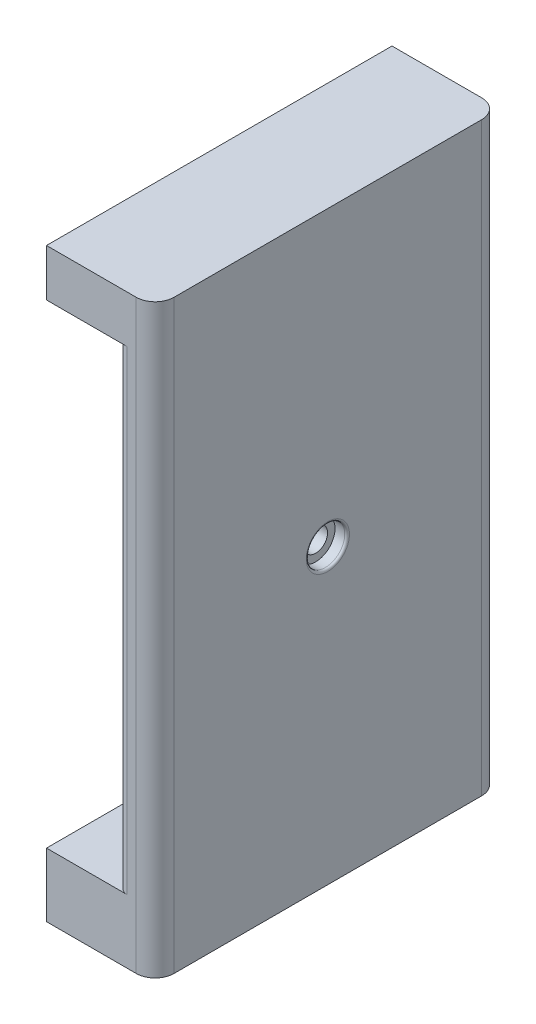
SolidWorks part; units mm, degrees
note: The reader was unsure of these and kept them because the rebuilt part matched: shared geometry of "Sketch12<6>".
other "Markup1"
sketch "Sketch9" plane through (-25.745, 62.7203, -36.576) normal (-0.5706, 0.1284, -0.8112) x (-0.8147, 0.0363, 0.5788)
ref_plane "Front Plane" through (0, 0, 0) normal (0, 0, 1) x (1, 0, 0)
ref_plane "Top Plane" through (0, 0, 0) normal (0, 1, 0) x (1, 0, 0)
ref_plane "Right Plane" through (0, 0, 0) normal (1, 0, 0) x (0, 0, -1)
sketch "Sketch1" plane through (0, 0, 0) normal (0, 0, 1) x (1, 0, 0)
  line L0 (8.255, 0) -> (-8.255, 0) construction
  line L1 (20.255, 0) -> (-20.255, 0) construction
  line L2 (8.255, 0) -> (8.255, 18.25)
  line L3 (8.255, 18.25) -> (20.255, 18.25)
  line L4 (20.255, 18.25) -> (20.255, 0)
  line L5 (8.255, 0) -> (20.255, 0)
  point P4 (0, 0)
  point P8 (0, 0)
  dimension "D1" = 16.51
  dimension "D2" = 12
  dimension "D3" = 18.25
revolve "Revolve1" add sketch "Sketch1" angle 360 about L5
sketch "Sketch2" plane through (8.255, 0, 0) normal (-1, 0, 0) x (0, 0, 1)
  circle A0 centre (0, 0) radius 3.7145
  dimension "D1" = 7.429
extrude "Cut-Extrude1" cut sketch "Sketch2" against normal blind 8.5725
sketch "Sketch3" plane through (20.255, 0, 0) normal (1, 0, 0) x (0, 0, -1)
  line L1 (13.175, -55) -> (-13.175, -55) construction
  line L2 (13.175, -55) -> (13.175, 55) construction
  line L3 (13.175, 55) -> (-13.175, 55) construction
  line L4 (-13.175, -55) -> (-13.175, 55) construction
  line L5 (13.175, -55) -> (-13.175, 55) construction
  line L6 (13.175, 55) -> (-13.175, -55) construction
  line L14 (6.6, 0) -> (-6.6, 0) construction
  line L15 (13.175, -55) -> (-13.175, 55) construction
  line L16 (13.175, 55) -> (-13.175, -55) construction
  line L17 (13.175, 55) -> (-13.175, 55) construction
  line L28 (-36.576, 0) -> (36.576, 0) construction
  line L33 (36.576, -62) -> (-36.576, -62)
  line L34 (36.576, -62) -> (36.576, 62)
  line L35 (36.576, 62) -> (-36.576, 62)
  line L36 (-36.576, -62) -> (-36.576, 62)
  line L37 (36.576, -62) -> (-36.576, 62) construction
  line L38 (36.576, 62) -> (-36.576, -62) construction
  point P0 (0, 0)
  point P11 (0, 0)
  point P12 (0, 0)
  dimension "D3" = 124
  dimension "D4" = 73.152
  dimension "D9" = 110
  dimension "D1" = 73.152
  dimension "D2" = 26.35
extrude "Boss-Extrude1" add sketch "Sketch3" along normal blind 8 separate body
sketch "Sketch4" plane through (20.255, 0, 0) normal (-1, 0, 0) x (0, 0, 1)
  line L0 (-19.575, 55) -> (-6.775, 55) construction
  line L1 (13.175, -55) -> (-13.175, -55) construction
  line L2 (13.175, -55) -> (13.175, 55) construction
  line L3 (13.175, 55) -> (-13.175, 55) construction
  line L4 (-13.175, -55) -> (-13.175, 55) construction
  line L5 (13.175, -55) -> (-13.175, 55) construction
  line L6 (13.175, 55) -> (-13.175, -55) construction
  circle A0 centre (-13.175, 55) radius 4.75
  circle A1 centre (13.175, -55) radius 4.75
  circle A2 centre (13.175, 55) radius 4.75
  circle A3 centre (-13.175, -55) radius 4.75
  circle A5 centre (-13.175, 55) radius 6.4
  circle A6 centre (13.175, 55) radius 6.4
  circle A7 centre (13.175, -55) radius 6.4
  circle A8 centre (-13.175, -55) radius 6.4
  point P6 (0, 0)
  dimension "D1" = 9.5
  dimension "D2" = 12.8
  dimension "D3" = 26.35
  dimension "D4" = 110
sketch "Sketch5" plane through (8.255, 0, 0) normal (-1, 0, 0) x (0, 0, 1)
  circle A0 centre (0, 0) radius 18.25
  dimension "D1" = 36.5
fillet "Fillet1" radius 4 2 edges at (28.255, 0, -36.576) (28.255, 0, 36.576)
sketch "Sketch6" plane through (8.255, 0, 0) normal (-1, 0, 0) x (0, 0, 1)
  circle A2 centre (0, 0) radius 13.15
  dimension "D1" = 26.3
extrude "Cut-Extrude2" cut sketch "Sketch6" against normal blind 12
ref_plane "Plane1" through (0, 0, 38) normal (0, 0, 1) x (1, 0, 0)
ref_plane "Plane2" through (19.255, 0, 0) normal (-1, 0, 0) x (0, 0, 1)
sketch "Sketch12" plane through (28.255, 0, 0) normal (1, 0, 0) x (0, 0, -1)
  circle A0 centre (0, 0) radius 4.075
  circle A1 centre (0, 0) radius 2.5
  dimension "D1" = 8.15
  dimension "D2" = 5
extrude "Cut-Extrude6" cut sketch "Sketch12" against normal blind 2.56 contours A0
extrude "Cut-Extrude7" cut sketch "Sketch12<6>" against normal up to surface (8 mm away) contours A1 up to face at (20.255, 0, 0)
sketch "Sketch12<6>" plane through (28.255, 0, 0) normal (1, 0, 0) x (0, 0, -1) same geometry as "Sketch12"
fillet "Fillet2" radius 0.5 1 edges at (28.255, 4.075, 0)
combine bodies "Combine1" operation type add bodies to combine 124 127
sketch "Sketch13" plane through (20.255, 0, 0) normal (-1, 0, 0) x (0, 0, 1)
  line L0 (-36.576, -62) -> (-36.576, 62) construction
  line L6 (-36.576, -48.5) -> (36.576, -48.5)
  line L7 (-36.576, -48.5) -> (-36.576, -62)
  line L8 (-36.576, -62) -> (36.576, -62)
  line L9 (36.576, -48.5) -> (36.576, -62)
  line L10 (36.576, -62) -> (36.576, 62) construction
  line L11 (-36.576, -62) -> (36.576, -62) construction
  line L13 (-36.576, 62) -> (36.576, 62)
  line L14 (-36.576, 62) -> (-36.576, 52)
  line L15 (-36.576, 52) -> (36.576, 52)
  line L16 (36.576, 62) -> (36.576, 52)
  dimension "D1" = 13.5
  dimension "D2" = 10
extrude "Boss-Extrude3" add sketch "Sketch13" along normal blind 15
fillet "Fillet3" radius 2 3 edges at (20.255, 1.75, -36.576) (20.255, -18.25, 0) (20.255, 1.75, 36.576)
sketch "Sketch14" plane through (0, -62, 0) normal (0, -1, 0) x (1, 0, 0)
  line L0 (28.255, 0) -> (-41.715, 0) construction
  line L1 (28.255, -32.576) -> (28.255, 32.576) construction
  line L3 (18.52, -12.75) -> (-31.98, -12.75) construction
  line L4 (18.52, -12.75) -> (18.52, 12.75) construction
  line L5 (18.52, 12.75) -> (-31.98, 12.75) construction
  line L6 (-31.98, -12.75) -> (-31.98, 12.75) construction
  line L7 (18.52, -12.75) -> (-31.98, 12.75) construction
  line L8 (18.52, 12.75) -> (-31.98, -12.75) construction
  circle A0 centre (18.52, 12.75) radius 3.7138
  circle A1 centre (18.52, -12.75) radius 3.7138
  point P6 (-6.73, 0)
  dimension "D4" = 7.4275
  dimension "D1" = 69.97
  dimension "D2" = 50.5
  dimension "D3" = 25.5
extrude "Cut-Extrude8" cut sketch "Sketch14" against normal blind 9.5
